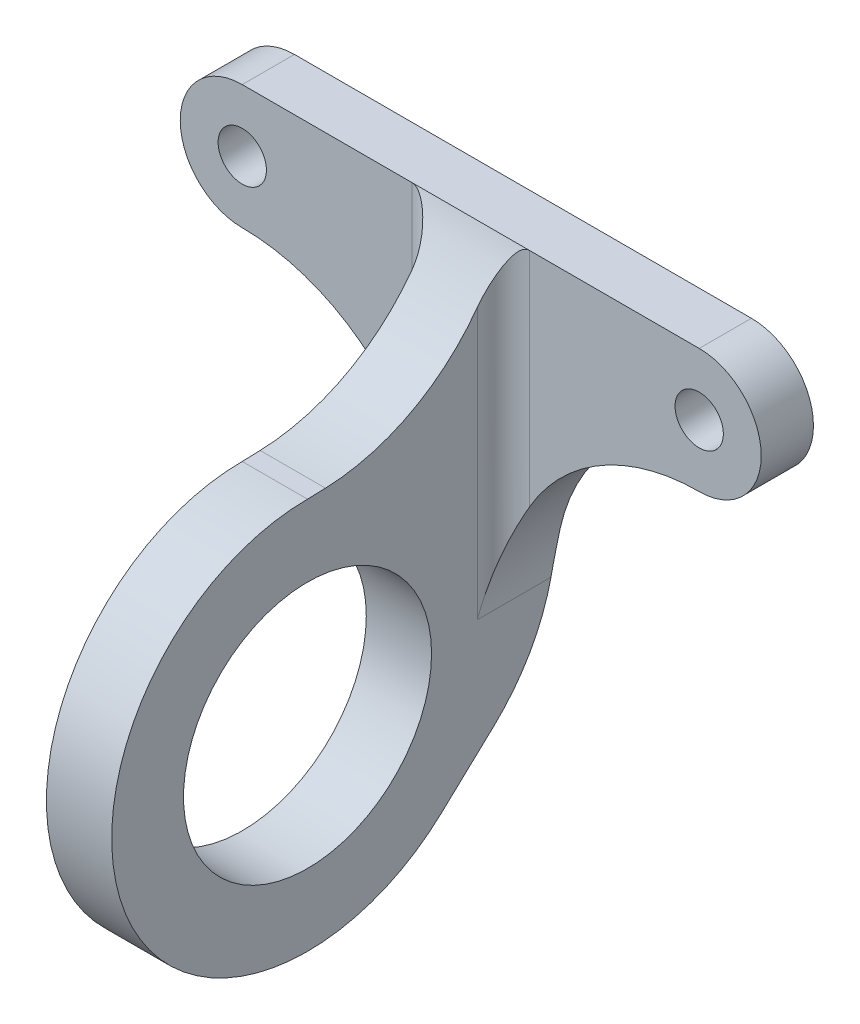
SolidWorks part; units mm, degrees
ref_plane "Front Plane" through (0, 0, 0) normal (0, 0, 1) x (1, 0, 0)
ref_plane "Top Plane" through (0, 0, 0) normal (0, 1, 0) x (1, 0, 0)
ref_plane "Right Plane" through (0, 0, 0) normal (1, 0, 0) x (0, 0, -1)
sketch "Sketch1" plane through (0, 0, 0) normal (0, 0, 1) x (1, 0, 0)
  line L1 (-17.5, 4.75) -> (17.5, 4.75)
  line L3 (-17.5, -4.75) -> (17.5, -4.75)
  circle A0 centre (-17.5, 0) radius 1.85
  circle A1 centre (17.5, 0) radius 1.85
  arc A2 (-17.5, 4.75) -> (-17.5, -4.75) centre (-17.5, 0) ccw
  arc A3 (17.5, -4.75) -> (17.5, 4.75) centre (17.5, 0) ccw
  dimension "D3" = 3.7
  dimension "D4" = 9.5
  dimension "D1" = 35
  dimension "D2" = 17.5
extrude "Boss-Extrude1" add sketch "Sketch1" along normal blind 4
sketch "Sketch2" plane through (0, 0, 0) normal (1, 0, 0) x (0, 0, -1)
  line L0 (-19, -5.25) -> (-4, -4.75)
  line L1 (-4, 4.75) -> (-4, -4.75) construction
  line L2 (-4, 4.75) -> (0, 4.75) construction
  line L3 (-4, 4.75) -> (0, 4.75)
  line L4 (-19, -20.25) -> (0, 4.75) construction
  line L5 (-4, -4.75) -> (-4, 4.75)
  line L6 (0, 4.75) -> (0, -4.6725)
  line L8 (0, -4.6725) -> (0, -23.0152)
  line L9 (0, -23.0152) -> (-8.752, -31.2035)
  circle A0 centre (-19, -20.25) radius 9.5
  arc A1 (-19, -5.25) -> (-8.752, -31.2035) centre (-19, -20.25) ccw
  dimension "D1" = 15
  dimension "D3" = 19
  dimension "D4" = 30
  dimension "D2" = 25
extrude "Boss-Extrude2" add sketch "Sketch2" along normal mid plane 5
fillet "Fillet1" radius 15 2 edges at (0, -4.75, 4) (0, -23.0152, 0)
fillet "Fillet2" radius 15 2 edges at (-2.5, -4.75, 2) (2.5, -4.75, 2)
fillet "Fillet3" radius 2 2 edges at (-2.5, -7.5, 4) (2.5, -7.5, 4)
